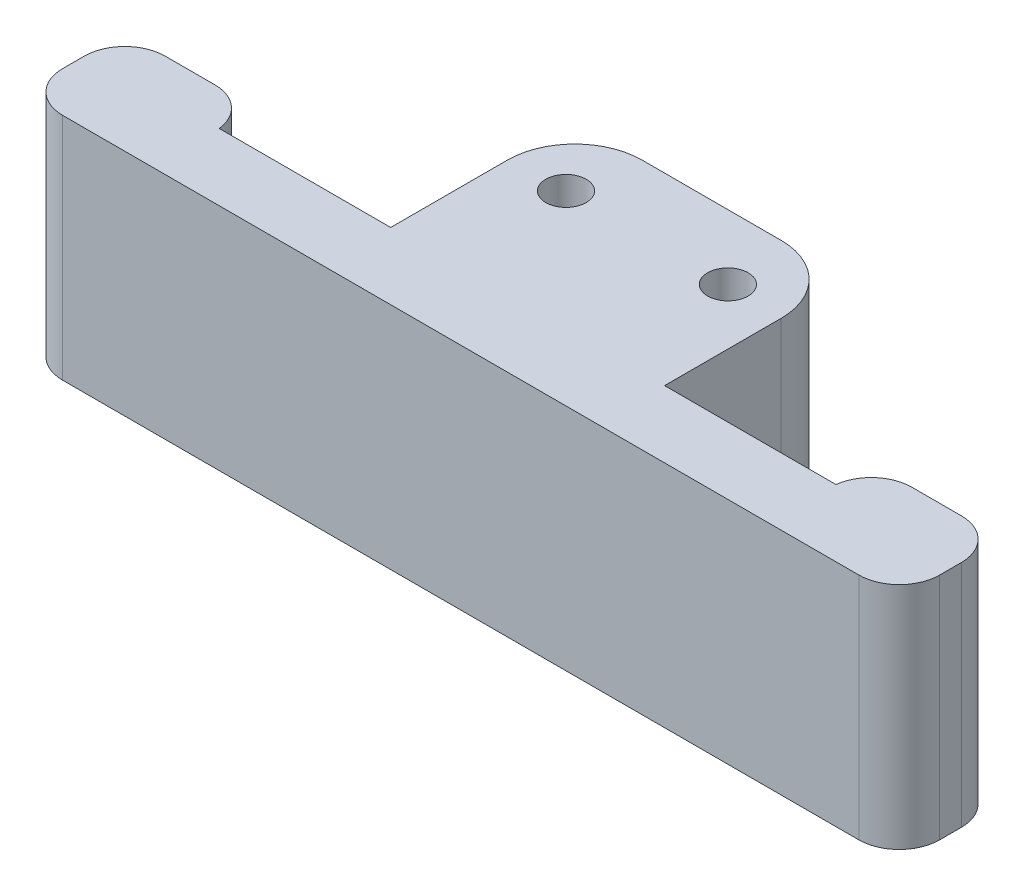
SolidWorks part; units mm, degrees
ref_plane "Спереди" through (0, 0, 0) normal (0, 0, 1) x (1, 0, 0)
ref_plane "Сверху" through (0, 0, 0) normal (0, 1, 0) x (1, 0, 0)
ref_plane "Справа" through (0, 0, 0) normal (1, 0, 0) x (0, 0, -1)
sketch "Sketch1" plane through (0, 0, 0) normal (0, 1, 0) x (1, 0, 0)
  line L0 (0, 0) -> (-6, 0) construction
  line L2 (-32.5, -13.8) -> (32.5, -13.8)
  line L3 (32.5, -13.8) -> (32.5, -6.2)
  line L4 (10.15, -6.2) -> (10.15, 4.8)
  line L5 (10.15, 4.8) -> (-10.15, 4.8)
  line L6 (-10.15, 4.8) -> (-10.15, -8.84)
  line L7 (0, 0) -> (6, 0) construction
  line L8 (32.5, -6.2) -> (22.85, -6.2)
  line L11 (22.85, -6.2) -> (22.85, -8.84)
  line L12 (22.85, -8.84) -> (10.15, -8.84)
  line L13 (10.15, -8.84) -> (10.15, -6.2)
  line L14 (-10.15, -8.84) -> (-22.85, -8.84)
  line L15 (-22.85, -8.84) -> (-22.85, -6.2)
  line L16 (-22.85, -6.2) -> (-32.5, -6.2)
  line L17 (-32.5, -6.2) -> (-32.5, -13.8)
  circle A0 centre (-6, 0) radius 1.5
  circle A1 centre (6, 0) radius 1.5
  point P0 (0, 0)
  dimension "D4" = 3
  dimension "D3" = 12
extrude "Boss-Extrude1" add sketch "Sketch1" along normal blind 17
sketch "Sketch2" plane through (0, 0, 0) normal (0, -1, 0) x (1, 0, 0)
  circle A0 centre (-3.1, 10) radius 1
  circle A1 centre (-29.9, 10) radius 1
  circle A2 centre (3.1, 10) radius 1
  circle A3 centre (29.9, 10) radius 1
  circle A4 centre (3.1, 10) radius 1 construction
  circle A5 centre (-3.1, 10) radius 1 construction
  circle A6 centre (-29.9, 10) radius 1 construction
  circle A7 centre (29.9, 10) radius 1 construction
extrude "Cut-Extrude1" cut sketch "Sketch2" against normal blind 12
fillet "Fillet2" radius 5 2 edges at (10.15, 8.5, -4.8) (-10.15, 8.5, -4.8)
fillet "Fillet3" radius 3 6 edges at (-32.5, 8.5, 13.8) (32.5, 8.5, 13.8) (32.5, 8.5, 6.2) (22.85, 8.5, 6.2) (-22.85, 8.5, 6.2) (-32.5, 8.5, 6.2)
